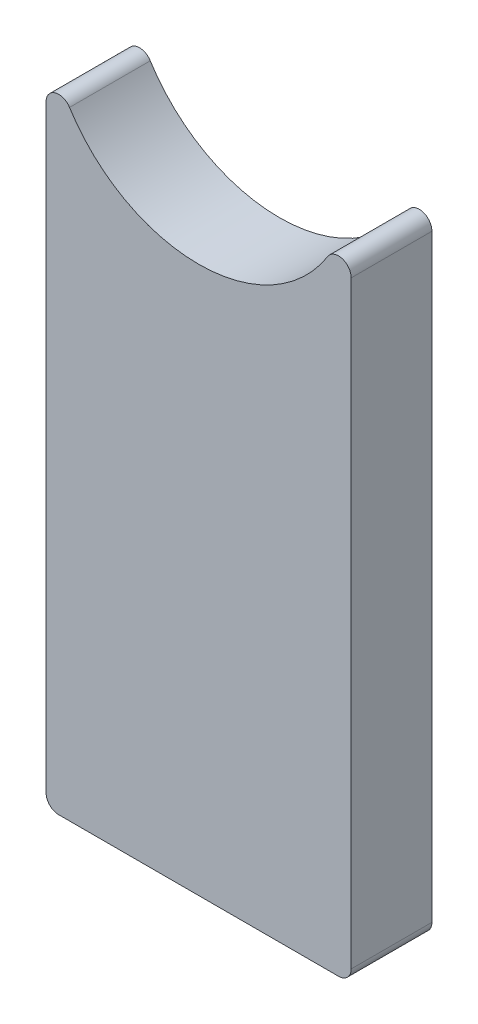
SolidWorks part; units mm, degrees
ref_plane "Front Plane" through (0, 0, 0) normal (0, 0, 1) x (1, 0, 0)
ref_plane "Top Plane" through (0, 0, 0) normal (0, 1, 0) x (1, 0, 0)
ref_plane "Right Plane" through (0, 0, 0) normal (1, 0, 0) x (0, 0, -1)
sketch "Sketch1" plane through (0, 0, 0) normal (0, 0, 1) x (1, 0, 0)
  line L0 (-83.1649, 19.4139) -> (-83.1649, -28.6579)
  line L1 (-83.1649, -28.6579) -> (-59.1649, -28.6579)
  line L2 (-59.1649, -28.6579) -> (-59.1649, 19.4139)
  arc A0 (-61.011, 19.9468) -> (-81.3187, 19.9468) centre (-71.1649, 26.3421) cw
  arc A1 (-59.1649, 19.4139) -> (-61.011, 19.9468) centre (-60.1649, 19.4139) ccw
  arc A2 (-83.1649, 19.4139) -> (-81.3187, 19.9468) centre (-82.1649, 19.4139) cw
  dimension "D1" = 24
  dimension "D3" = 1
  dimension "D4" = 1
  dimension "D2" = 55
extrude "Boss-Extrude1" add sketch "Sketch1" along normal blind 6.35
fillet "Fillet1" radius 1 2 edges at (-59.1649, -28.6579, 3.175) (-83.1649, -28.6579, 3.175)
